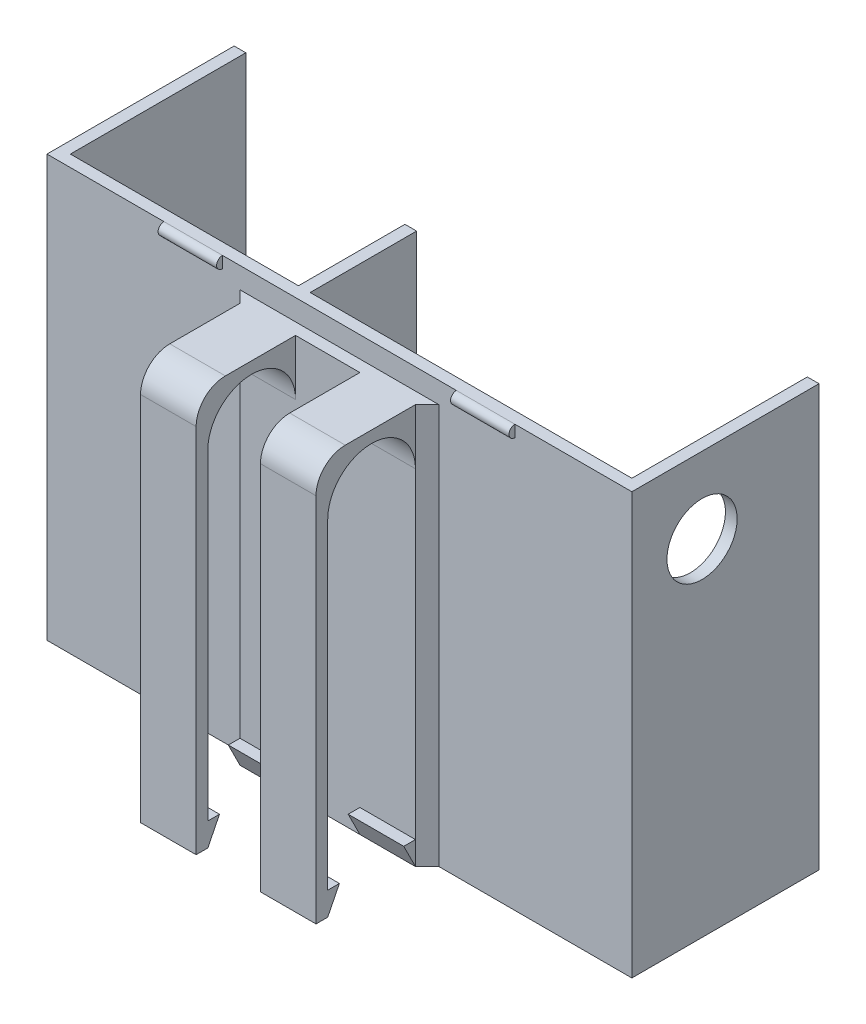
SolidWorks part; units mm, degrees
note: The reader was unsure of these and kept them because the rebuilt part matched: shared geometry of "Sketch3<3>", "Sketch5<3>", "Sketch5<4>".
ref_plane "Front Plane" through (0, 0, 0) normal (0, 0, 1) x (1, 0, 0)
ref_plane "Top Plane" through (0, 0, 0) normal (0, 1, 0) x (1, 0, 0)
ref_plane "Right Plane" through (0, 0, 0) normal (1, 0, 0) x (0, 0, -1)
sketch "Sketch1" plane through (0, 0, 0) normal (1, 0, 0) x (0, 0, -1)
  line L0 (0, 0) -> (0, 58.9)
  line L1 (0, 58.9) -> (15, 58.9)
  line L2 (15, 58.9) -> (15, 0)
  line L3 (0, 0) -> (-2, 0)
  line L4 (-2, 0) -> (-2, 58.9)
  line L5 (15, 0) -> (17, 0)
  line L6 (17, 0) -> (17, 58.9)
  line L7 (15, 0) -> (13, 4)
  line L8 (13, 4) -> (15, 4)
  line L9 (7.5, 68.4) -> (7.5, -6.29) construction
  line L10 (0, 0) -> (2, 4)
  line L11 (2, 4) -> (0, 4)
  line L12 (17, 58.9) -> (17, 68.4)
  line L13 (17, 68.4) -> (-2, 68.4)
  line L14 (-2, 68.4) -> (-2, 58.9)
  arc A0 (0, 58.9) -> (15, 58.9) centre (7.5, 58.9) cw
  arc A1 (-2, 58.9) -> (17, 58.9) centre (7.5, 58.9) cw
  point P11 (7.5, 68.4)
  dimension "D3" = 2
  dimension "D5" = 2
  dimension "D4" = 4
  dimension "D1" = 68.4
  dimension "D6" = 9.5
  dimension "D2" = 15
extrude "Boss-Extrude1" add sketch "Sketch1" against normal blind 30 contours A1 L4 L3 L0 A0 L2 L5 L6 | L9 A1 L4 L3 L0 A0 | L10 L11 L0 | L8 L7 L2 | L13 A1 L12 | L14 A1 L13
fillet "Fillet1" radius 5 1 edges at (-15, 68.4, 2)
sketch "Sketch2" plane through (0, 0, 2) normal (0, 0, 1) x (1, 0, 0)
  line L0 (-15, 68.4) -> (-15, 0) construction
  line L2 (-30, 0) -> (0, 0) construction
  line L4 (-20.5, 68.4) -> (-20.5, 0)
  line L5 (-20.5, 68.4) -> (-9.5, 68.4)
  line L6 (-15, 68.4) -> (-15, 0)
  line L7 (-9.5, 0) -> (-20.5, 0)
  line L8 (-9.5, 68.4) -> (-9.5, 0)
  dimension "D1" = 5.5
extrude "Cut-Extrude1" cut sketch "Sketch2" against normal blind 17
sketch "Sketch3" plane through (0, 0, -17) normal (0, 0, -1) x (-1, 0, 0)
  line L0 (15, 74) -> (15, 0) construction
  line L1 (63, 72) -> (65, 72)
  line L2 (30, 0) -> (0, 0) construction
  line L3 (-35, 0) -> (65, 0)
  line L4 (65, 0) -> (65, 74)
  line L5 (65, 74) -> (-35, 74)
  line L6 (-35, 0) -> (-35, 74)
  line L7 (-33, 2) -> (63, 2)
  line L8 (-33, 2) -> (-33, 72)
  line L9 (-33, 72) -> (63, 72)
  line L10 (63, 2) -> (63, 72)
  line L11 (-33, 2) -> (63, 72) construction
  line L12 (-33, 72) -> (63, 2) construction
  line L13 (-33, 72) -> (-35, 72)
  point P2 (15, 37)
  point P3 (15, 37)
  line M10 (0, 68.4) -> (0, 0)
  line M11 (0, 0) -> (30, 0)
  line M12 (30, 0) -> (30, 68.4)
  line M14 (30, 68.4) -> (0, 68.4)
  dimension "D1" = 100
  dimension "D2" = 74
  dimension "D3" = 70
  dimension "D4" = 96
extrude "Boss-Extrude3" add sketch "Sketch3" along normal blind 2 contours L7 L10 L9 L8 M10 M14 M12 | L10 L7 L3 L4 L5 L6 L8 L9 M12 M10 | L7 M10 M12 M14 | L7 M10 M11 M12
extrude "Boss-Extrude4" add sketch "Sketch3<3>" along normal blind 32 contours L8 L13 L6 L3 L7 M10 | L10 L7 L3 L4 L1 M12 | L7 M10 M11 M12
sketch "Sketch3<3>" plane through (0, 0, -17) normal (0, 0, -1) x (-1, 0, 0) same geometry as "Sketch3"
sketch "Sketch4" plane through (0, 0, -19) normal (0, 0, -1) x (-1, 0, 0)
  line L0 (63, 2) -> (63, 72) construction
  line L5 (-33, 2) -> (63, 2) construction
  line L6 (22, 2) -> (24, 2)
  line L7 (22, 2) -> (22, 72)
  line L8 (22, 72) -> (24, 72)
  line L9 (24, 2) -> (24, 72)
  line L10 (-33, 72) -> (63, 72) construction
  dimension "D1" = 2
  dimension "D2" = 39
extrude "Boss-Extrude5" add sketch "Sketch4" along normal blind 18.2
ref_plane "Plane1" through (-15, 0, 0) normal (-1, 0, 0) x (0, 0, 1)
sketch "Sketch5" plane through (-15, 0, 0) normal (-1, 0, 0) x (0, 0, 1)
  line L0 (-17, 72) -> (-17, 70)
  line L1 (-17, 0) -> (-17, 72) construction
  line L2 (-48.8, 0) -> (-46.8, 0)
  line L4 (-49, 0) -> (-17, 0) construction
  line L5 (-49, 0) -> (-49, 72) construction
  arc A0 (-17, 72) -> (-17, 70) centre (-17, 71) cw
  arc A1 (-48.8, 0) -> (-46.8, 0) centre (-47.8, 0) ccw
  dimension "D1" = 1
  dimension "D2" = 2
  dimension "D3" = 1.2
extrude "Boss-Extrude6" add sketch "Sketch5" along normal blind 10 and the other way blind 10 contours L2 A1
extrude "Boss-Extrude7" add sketch "Sketch5<3>" along normal blind 10 from offset 20 contours A0 L0
sketch "Sketch5<3>" plane through (-15, 0, 0) normal (-1, 0, 0) x (0, 0, 1) same geometry as "Sketch5"
extrude "Boss-Extrude8" add sketch "Sketch5<4>" against normal blind 10 from offset 20 contours A0 L0 offset against normal yes
sketch "Sketch5<4>" plane through (-15, 0, 0) normal (-1, 0, 0) x (0, 0, 1) same geometry as "Sketch5"
chamfer "Chamfer1" distance 2 angle 45 2 edges at (-30, 34.2, -17) (0, 34.2, -17)
sketch "Sketch6" plane through (35, 0, 0) normal (1, 0, 0) x (0, 0, -1)
  line L1 (49, 72) -> (17, 72) construction
  line L3 (17, 0) -> (17, 72) construction
  circle A0 centre (29, 59) radius 6
  dimension "D1" = 12
  dimension "D2" = 13
  dimension "D3" = 12
extrude "Cut-Extrude2" cut sketch "Sketch6" against normal up to next
